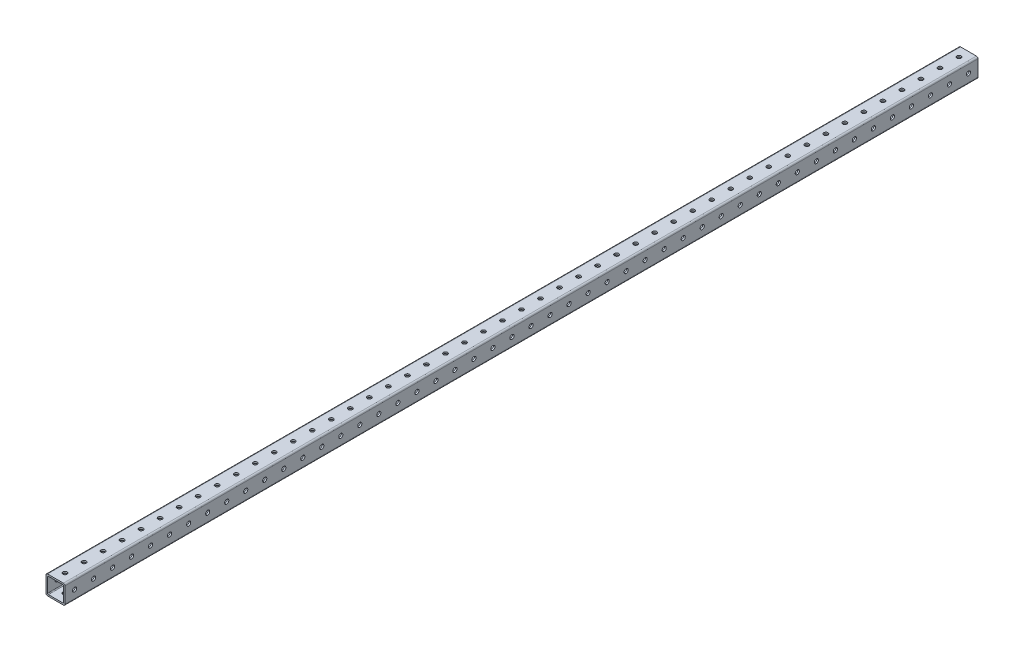
SolidWorks part; units mm, degrees
ref_plane "Front Plane" through (0, 0, 0) normal (0, 0, 1) x (1, 0, 0)
ref_plane "Top Plane" through (0, 0, 0) normal (0, 1, 0) x (1, 0, 0)
ref_plane "Right Plane" through (0, 0, 0) normal (1, 0, 0) x (0, 0, -1)
sketch "Sketch1" plane through (0, 0, 0) normal (0, 0, 1) x (1, 0, 0)
  line L0 (19.05, 0) -> (-19.05, 0) construction
  line L1 (0, -19.05) -> (0, 19.05) construction
  point P0 (0, 15.875)
  point P4 (0, 0)
  point P8 (0, 0)
  dimension "Width" = 38.1
  dimension "Height" = 38.1
  dimension "Wall" = 3.175
sketch "Sketch2" plane through (0, 0, 0) normal (1, 0, 0) x (0, 0, -1)
  line L0 (914.4, 0) -> (-914.4, 0) construction
  line L2 (-895.35, 4.1656) -> (-895.35, -4.1656) construction
  point P0 (-857.25, 0)
  point P3 (0, 0)
  point P7 (-895.35, 0)
sketch "Sketch3" plane through (0, 0, 0) normal (0, 0, 1) x (1, 0, 0)
  line L0 (0, -19.05) -> (0, 19.05) construction
  line L1 (15.875, 19.05) -> (-15.875, 19.05)
  line L2 (19.05, 15.875) -> (19.05, -15.875)
  line L3 (15.875, -19.05) -> (-15.875, -19.05)
  line L4 (-19.05, 15.875) -> (-19.05, -15.875)
  line L5 (19.05, 19.05) -> (-19.05, -19.05) construction
  line L6 (19.05, -19.05) -> (-19.05, 19.05) construction
  line L7 (-14.2875, -15.875) -> (14.2875, -15.875)
  line L8 (-15.875, -14.2875) -> (-15.875, 14.2875)
  line L9 (-14.2875, 15.875) -> (14.2875, 15.875)
  line L10 (15.875, -14.2875) -> (15.875, 14.2875)
  line L11 (-15.875, -15.875) -> (15.875, 15.875) construction
  line L12 (-15.875, 15.875) -> (15.875, -15.875) construction
  arc A0 (19.05, -15.875) -> (15.875, -19.05) centre (15.875, -15.875) cw
  arc A1 (15.875, 19.05) -> (19.05, 15.875) centre (15.875, 15.875) cw
  arc A2 (-15.875, 19.05) -> (-19.05, 15.875) centre (-15.875, 15.875) ccw
  arc A3 (-15.875, -19.05) -> (-19.05, -15.875) centre (-15.875, -15.875) cw
  arc A4 (-14.2875, -15.875) -> (-15.875, -14.2875) centre (-14.2875, -14.2875) cw
  arc A5 (14.2875, -15.875) -> (15.875, -14.2875) centre (14.2875, -14.2875) ccw
  arc A6 (14.2875, 15.875) -> (15.875, 14.2875) centre (14.2875, 14.2875) cw
  arc A7 (-15.875, 14.2875) -> (-14.2875, 15.875) centre (-14.2875, 14.2875) cw
  point P0 (0, 0)
  point P5 (0, 0)
  dimension "D1" = 3.175
  dimension "D2" = 1.5875
extrude "Boss-Extrude1" add sketch "Sketch3" along normal up to vertex (914.4 mm away) and the other way up to vertex (914.4 mm away) up to point (0, 0, 914.4) other way up to point (0, 0, -914.4)
sketch "Sketch4" plane through (0, 0, 0) normal (1, 0, 0) x (0, 0, -1)
  circle A0 centre (-895.35, 0) radius 4.1656
extrude "Cut-Extrude1" cut sketch "Sketch4" against normal through all both and the other way through all
pattern_linear "LPattern1" count 48 spacing 38.1 along (0, 0, -1) of "Cut-Extrude1"
ref_axis "Axis1" through (0, 0, -670.56) along (0, 0, 1)
pattern_circular "CirPattern1" count 2 every 90 about axis through (0, 0, -670.56) along (0, 0, 1) of "LPattern1", "Cut-Extrude1"
equation "\"D3@LPattern1\"=\"Hole to Hole@Sketch2\""
equation "\"D1@LPattern1\"=\"Length@Sketch2\"/\"Hole to Hole@Sketch2\""
